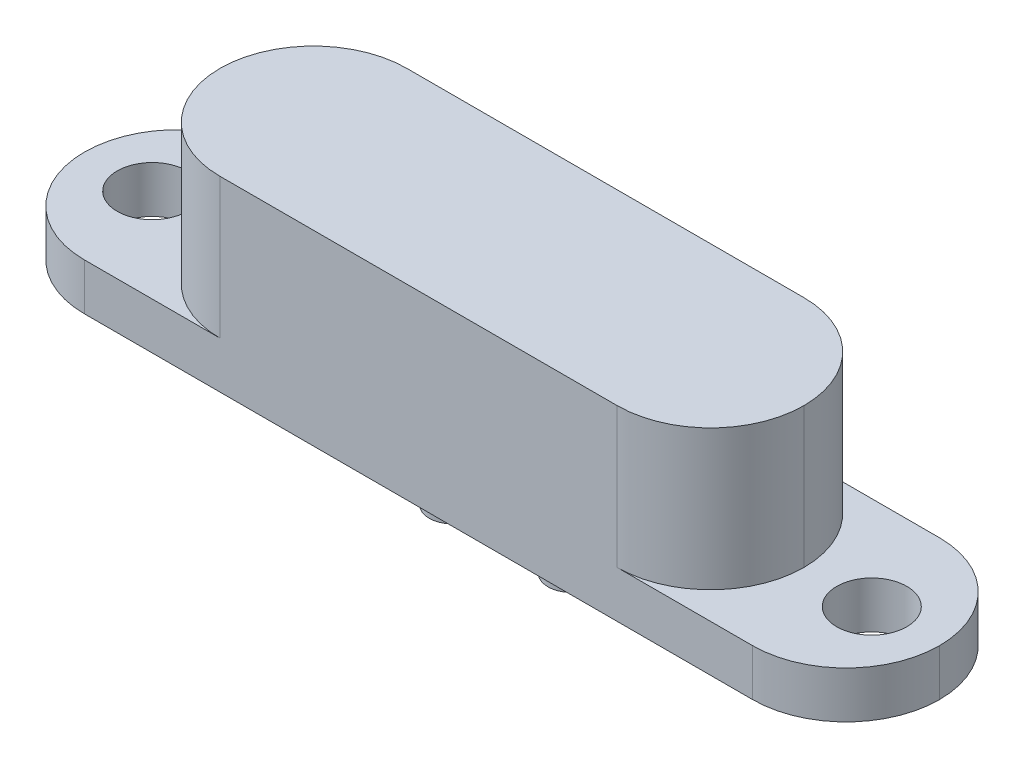
SolidWorks part; units mm, degrees
ref_plane "前视基准面" through (0, 0, 0) normal (0, 0, 1) x (1, 0, 0)
ref_plane "上视基准面" through (0, 0, 0) normal (0, 1, 0) x (1, 0, 0)
ref_plane "右视基准面" through (0, 0, 0) normal (1, 0, 0) x (0, 0, -1)
other "Configuration Table"
sketch "草图1" plane through (0, 0, 0) normal (0, 1, 0) x (1, 0, 0)
  line L1 (-9.15, -2) -> (9.15, -2)
  line L2 (-9.15, -2) -> (-9.15, 2)
  line L3 (-9.15, 2) -> (9.15, 2)
  line L4 (9.15, -2) -> (9.15, 2)
  line L5 (-9.15, -2) -> (9.15, 2) construction
  line L6 (-9.15, 2) -> (9.15, -2) construction
  line L7 (-6.25, -2) -> (6.25, -2)
  line L8 (-6.25, -2) -> (-6.25, 2)
  line L9 (-6.25, 2) -> (6.25, 2)
  line L10 (6.25, -2) -> (6.25, 2)
  line L11 (-6.25, -2) -> (6.25, 2) construction
  line L12 (-6.25, 2) -> (6.25, -2) construction
  point P0 (0, 0)
  point P7 (0, 0)
  dimension "D1" = 4
  dimension "D2" = 18.3
  dimension "D3" = 12.5
extrude "凸台-拉伸1" add sketch "草图1" along normal blind 4 contours L8 L9 L10 L7
fillet "圆角1" radius 2 4 edges at (6.25, 2, -2) (6.25, 2, 2) (-6.25, 2, 2) (-6.25, 2, -2)
extrude "凸台-拉伸2" add sketch "草图1<3>" along normal blind 1 contours L2 L3 L4 L1
sketch "草图1<3>" plane through (0, 0, 0) normal (0, 1, 0) x (1, 0, 0) same geometry as "草图1"
fillet "圆角2" radius 2 4 edges at (9.15, 0.5, 2) (9.15, 0.5, -2) (-9.15, 0.5, 2) (-9.15, 0.5, -2)
sketch "草图2" plane through (0, 1, 0) normal (0, 1, 0) x (1, 0, 0)
  line L0 (-9.15, 0) -> (-6.25, 0) construction
  line L1 (6.25, 0) -> (9.15, 0) construction
  arc A0 (-6.25, 0) -> (-4.25, -2) centre (-4.25, 0) ccw construction
  circle A1 centre (-7.7, 0) radius 0.75
  arc A2 (4.25, -2) -> (6.25, 0) centre (4.25, 0) ccw construction
  circle A3 centre (7.7, 0) radius 0.75
  dimension "D1" = 1.5
extrude "切除-拉伸1" cut sketch "草图2" against normal through all
sketch "草图3" plane through (0, 0, 0) normal (0, -1, 0) x (1, 0, 0)
  line L0 (-1.27, 0) -> (0, 0) construction
  line L7 (0, 0) -> (1.27, 0) construction
  circle A0 centre (-1.27, 0) radius 0.5
  circle A1 centre (1.27, 0) radius 0.5
  point P0 (0, 0)
  dimension "D2" = 1
  dimension "D1" = 2.54
extrude "凸台-拉伸3" add sketch "草图3" along normal blind 5.6 from surface starting at face at (0, 4, 0)
sketch "草图4" plane through (0, 0, 0) normal (0, -1, 0) x (1, 0, 0)
  circle A0 centre (0, 0) radius 0.5
  dimension "D1" = 1
extrude "切除-拉伸2" cut sketch "草图4" against normal blind 0.1
